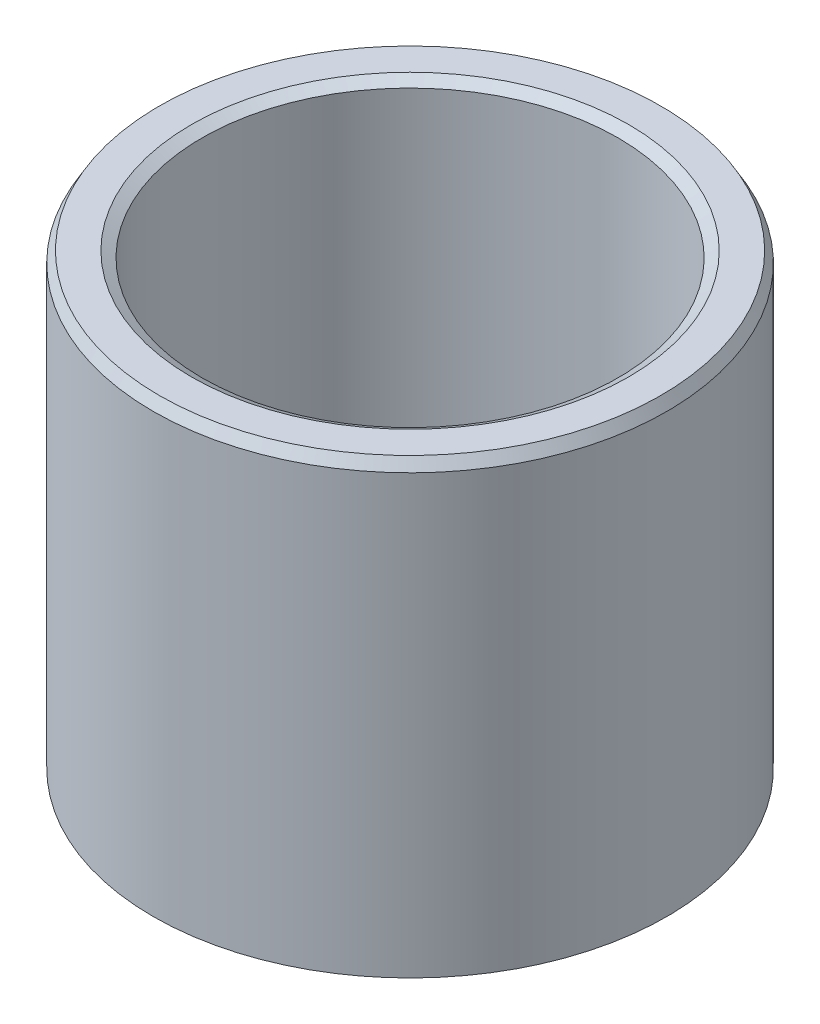
SolidWorks part; units mm, degrees
ref_plane "Front Plane" through (0, 0, 0) normal (0, 0, 1) x (1, 0, 0)
ref_plane "Top Plane" through (0, 0, 0) normal (0, 1, 0) x (1, 0, 0)
ref_plane "Right Plane" through (0, 0, 0) normal (1, 0, 0) x (0, 0, -1)
sketch "Sketch1" plane through (0, 0, 0) normal (0, 1, 0) x (1, 0, 0)
  circle A0 centre (0, 0) radius 42.5
  dimension "SLEEVE_OD" = 85
extrude "Boss-Extrude1" add sketch "Sketch1" along normal blind 75.1543
sketch "Sketch2" plane through (0, 0, 0) normal (0, 1, 0) x (1, 0, 0)
  circle A0 centre (0, 0) radius 34.4001
  dimension "BORE_D" = 68.8003
extrude "Cut-Extrude1" cut sketch "Sketch2" along normal through all
chamfer "Chamfer1" distance 1.7649 angle 30 4 edges at (0, 75.1543, 34.4001) (0, 0, 34.4001) (0, 0, 42.5) (0, 75.1543, 42.5) first distance on face at (0, 75.1543, 34.4001) first distance on face at (0, 0, 34.4001) first distance on face at (0, 75.1543, 42.5)
